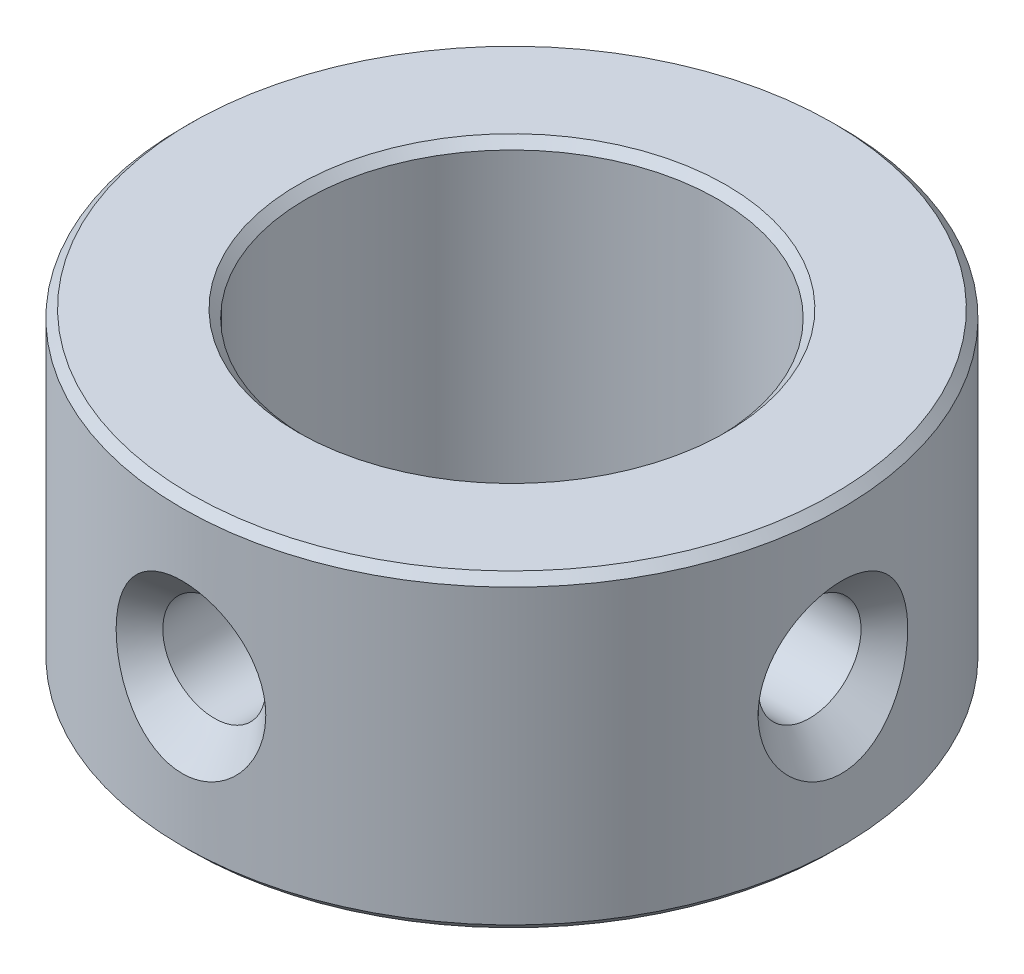
SolidWorks part; units mm, degrees
material "6061-T6 (SS)"
ref_plane "Front Plane" through (0, 0, 0) normal (0, 0, 1) x (1, 0, 0)
ref_plane "Top Plane" through (0, 0, 0) normal (0, 1, 0) x (1, 0, 0)
ref_plane "Right Plane" through (0, 0, 0) normal (1, 0, 0) x (0, 0, -1)
sketch "Profile Sketch" plane through (0, 0, 0) normal (0, 1, 0) x (1, 0, 0)
  circle A0 centre (0, 0) radius 5
  circle A1 centre (0, 0) radius 8
  dimension "InnerDia" = 10
  dimension "RefOuterDia" = 16
  dimension "DiaControl" = 3
extrude "Profile" add sketch "Profile Sketch" along normal mid plane 7.5
ref_plane "SetScrewPlane" through (0, 0, 8) normal (0, 0, 1) x (1, 0, 0)
hole_wizard " Tapped Hole1" positions "Sketch1" profile "Sketch2" tap size "M3x0.5" standard "ANSI Metric" end condition up to next
sketch "Sketch1" plane through (0, 0, 8) normal (0, 0, 1) x (1, 0, 0)
  point P0 (0, 0)
sketch "Sketch2" plane through (0, 0, 8) normal (1, 0, 0) x (0, -1, 0)
  line L0 (0, 0) -> (0, 3)
  line L1 (0, 3) -> (1.25, 3)
  line L2 (1.25, 3) -> (1.25, 0.775)
  line L3 (1.25, 0.775) -> (2.025, 0)
  line L5 (2.025, 0) -> (0, 0)
  line L6 (-1.25, 0.775) -> (-2.025, 0) construction
  line L11 (0, -6.35) -> (0, 107.95) construction
  dimension "Thru Tap Drill Dia." = 2.5
  dimension "Thru Tap Drill Depth" = 3
  dimension "Near C'Sink Dia." = 4.05
  dimension "Near C'Sink Angle" = 90
cosmetic thread "Hole Thread1" parameters "D2"=3
pattern_circular "Set Screw Circular Pattern" count 2 every 90 about axis through (0, 3.75, 0) along (0, -1, 0) of " Tapped Hole1" reverse direction yes
chamfer "Outer Chamfer" distance 0.2 angle 45 2 edges at (0, 3.75, 8) (0, -3.75, 8)
chamfer "Inner Chamfer" distance 0.2 angle 45 2 edges at (0, 3.75, 5) (0, -3.75, 5)
